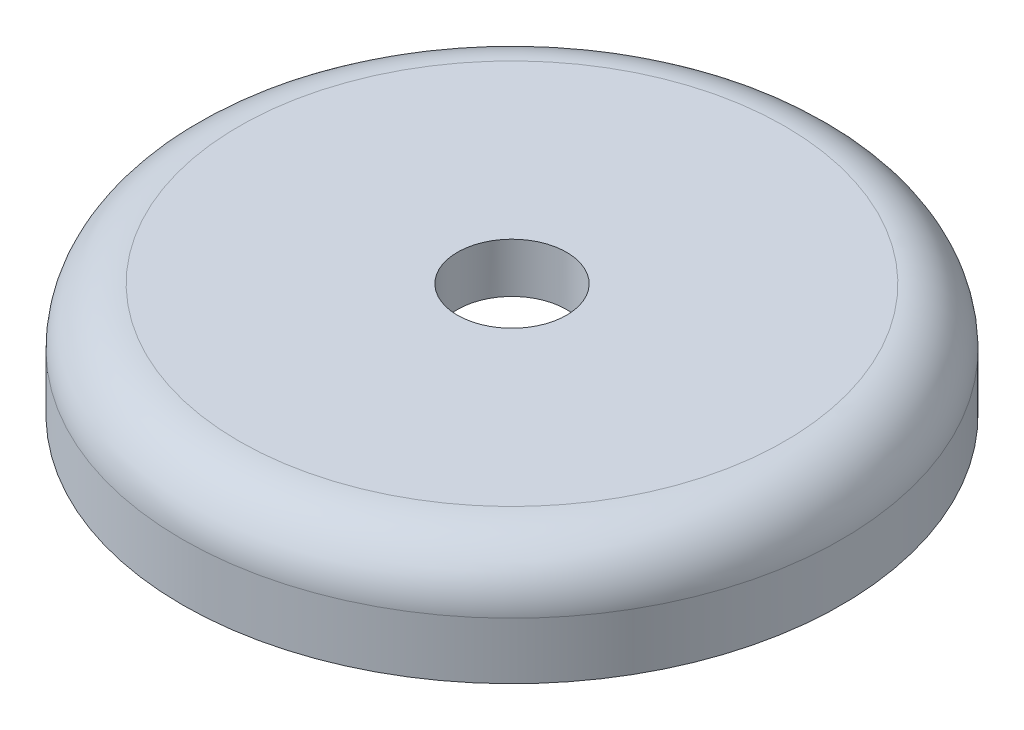
SolidWorks part; units mm, degrees
ref_plane "Front Plane" through (0, 0, 0) normal (0, 0, 1) x (1, 0, 0)
ref_plane "Top Plane" through (0, 0, 0) normal (0, 1, 0) x (1, 0, 0)
ref_plane "Right Plane" through (0, 0, 0) normal (1, 0, 0) x (0, 0, -1)
sketch "Sketch1" plane through (0, 0, 0) normal (0, 1, 0) x (1, 0, 0)
  circle A0 centre (0, 0) radius 59.055
  dimension "D1" = 118.11
extrude "Boss-Extrude1" add sketch "Sketch1" along normal blind 20.32
sketch "Sketch2" plane through (0, 20.32, 0) normal (0, 1, 0) x (1, 0, 0)
  circle A0 centre (0, 0) radius 9.779
  dimension "D1" = 19.558
extrude "Cut-Extrude1" cut sketch "Sketch2" against normal through all
fillet "Fillet1" radius 10.16 1 edges at (0, 20.32, 59.055)
shell "Shell2" thickness 5.08 removed face at (0, 0, 9.779)
sketch "Sketch3" plane through (0, 0, 0) normal (0, -1, 0) x (1, 0, 0)
  circle A0 centre (0, 0) radius 12.3877
sketch "Sketch4" plane through (0, 0, 0) normal (0, -1, 0) x (1, 0, 0)
  circle A0 centre (0, 0) radius 9.779
  circle A1 centre (0, 0) radius 14.859
extrude "Cut-Extrude3" cut sketch "Sketch4" against normal blind 11.43
fillet "Fillet3" radius 5.08 1 edges at (0, 11.43, -14.859)
equation "\"chalk_length\"= 2.95in"
equation "\"chalk_diameter\"= 0.47in"
equation "\"drum_diameter\"= 4.25in"
equation "\"drum_thickness\" = 0.2in"
equation "\"drum_height\"= 3.75in"
equation "\"axis_diameter\" = 0.5in"
equation "\"axis_grips\"= \"axis_diameter\" / 4"
equation "\"axis_insert_gap\"= \"axis_diameter\" / 4"
equation "\"tight_fit\" = 0.005in"
equation "\"normal_fit\" = 0.010in"
equation "\"loose_fit\" = 0.020in"
equation "\"D1@Sketch1\"=\"drum_diameter\" + 2*\"drum_thickness\""
equation "\"D1@Boss-Extrude1\"=\"carousel_height\"*2"
equation "\"top_diameter\"= \"drum_diameter\" - 2 * \"drum_thickness\" - \"loose_fit\""
equation "\"top_thickness\"= 0.2in"
equation "\"hexagonal_diameter\"= 0.75in'Can't be less than axis_diaemeter + top_thickness. Hexagonal diameter for top interface and chalk_slot"
equation "\"hexagonal_female_diameter\"= 0.10in'All hexagons use inscribed unless otherwise explicit"
equation "\"hexagonal_female_spacing\"= 0.10in"
equation "\"hexagonal_female_height\"= 0.15in"
equation "\"carousel_height\" = 0.4in"
equation "\"D1@Sketch2\"=\"hexagonal_diameter\" + \"loose_fit\""
equation "\"D1\"= \"carousel_height\""
equation "\"D1@Fillet1\"=\"carousel_height\""
equation "\"D1@Shell2\"=\"drum_thickness\""
equation "\"chalk_slot_diameter\"= 0.75in"
equation "\"chalk_slot_height\"= 2.95in"
equation "\"chalk_padding_gap\"= 0.10in"
equation "\"cap_height\" = 0.5in"
equation "\"cap_depth\" = 0.5in"
